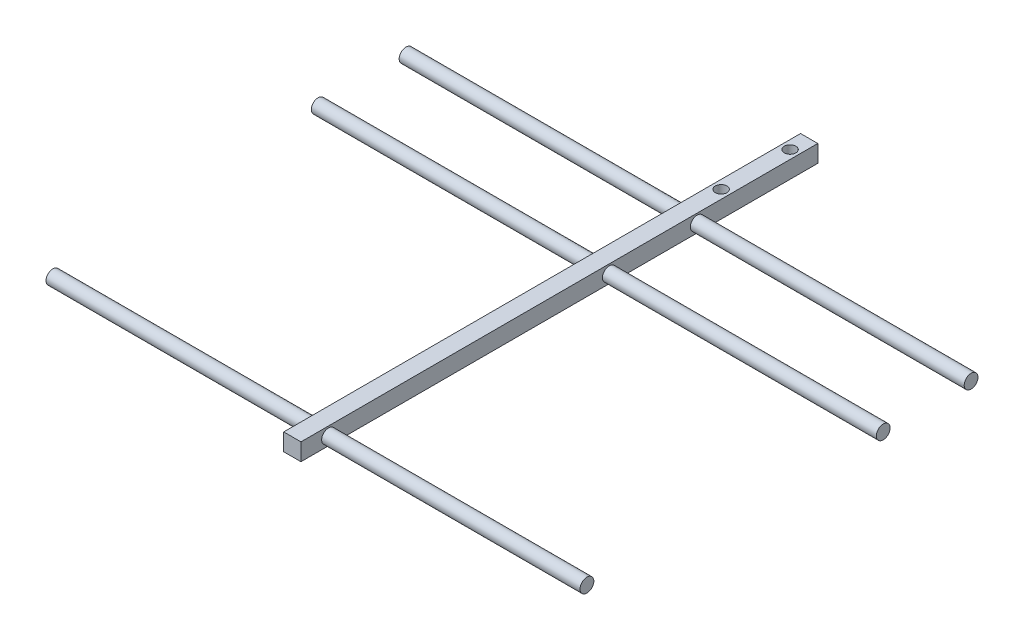
SolidWorks part; units mm, degrees
ref_plane "Front Plane" through (0, 0, 0) normal (0, 0, 1) x (1, 0, 0)
ref_plane "Top Plane" through (0, 0, 0) normal (0, 1, 0) x (1, 0, 0)
ref_plane "Right Plane" through (0, 0, 0) normal (1, 0, 0) x (0, 0, -1)
sketch "Sketch1" plane through (0, 0, 0) normal (0, 0, 1) x (1, 0, 0)
  line L1 (-5, 5) -> (5, 5)
  line L2 (-5, 5) -> (-5, -5)
  line L3 (-5, -5) -> (5, -5)
  line L4 (5, 5) -> (5, -5)
  line L5 (-5, 5) -> (5, -5) construction
  line L6 (-5, -5) -> (5, 5) construction
  point P0 (0, 0)
  dimension "D1" = 10
  dimension "D2" = 10
extrude "Boss-Extrude1" add sketch "Sketch1" along normal blind 300
sketch "Sketch3" plane through (0, 0, 0) normal (1, 0, 0) x (0, 0, -1)
  line L0 (-300, 0) -> (0, 0) construction
  line L1 (-300, -5) -> (-300, 5) construction
  line L2 (0, -5) -> (0, 5) construction
  circle A0 centre (-70, 0) radius 4
  circle A1 centre (-121, 0) radius 4
  circle A2 centre (-284, 0) radius 4
  dimension "D1" = 8
  dimension "D2" = 163
  dimension "D3" = 214
  dimension "D4" = 16
ref_plane "Plane1" through (35, 0, 0) normal (1, 0, 0) x (0, 0, -1)
sketch "Sketch9" plane through (0, 5, 0) normal (0, 1, 0) x (1, 0, 0)
  line L0 (0, 0) -> (0, -11.0993) construction
  line L1 (0, -11.0993) -> (0, -51.0993) construction
  circle A0 centre (0, -11.0993) radius 3.3845
  circle A1 centre (0, -51.0993) radius 3.3845
  dimension "D1" = 40
extrude "Cut-Extrude1" cut sketch "Sketch9" against normal through all
extrude "Boss-Extrude7" add sketch "Sketch3" along normal blind 155 and the other way blind 155 contours L0 A2 | A2 L0 region at (0, 1.6977, 284) region at (0, -1.6977, 284)
extrude "Boss-Extrude8" add sketch "Sketch3<3>" along normal blind 164 and the other way blind 164 contours L0 A0 | A0 L0 region at (0, 1.6977, 70) region at (0, -1.6977, 70)
sketch "Sketch3<3>" plane through (0, 0, 0) normal (1, 0, 0) x (0, 0, -1) same geometry as "Sketch3"
extrude "Boss-Extrude9" add sketch "Sketch3<4>" along normal blind 164 and the other way blind 164 contours A1 L0 | A1 region at (0, 1.6977, 121)
sketch "Sketch3<4>" plane through (0, 0, 0) normal (1, 0, 0) x (0, 0, -1) same geometry as "Sketch3"
